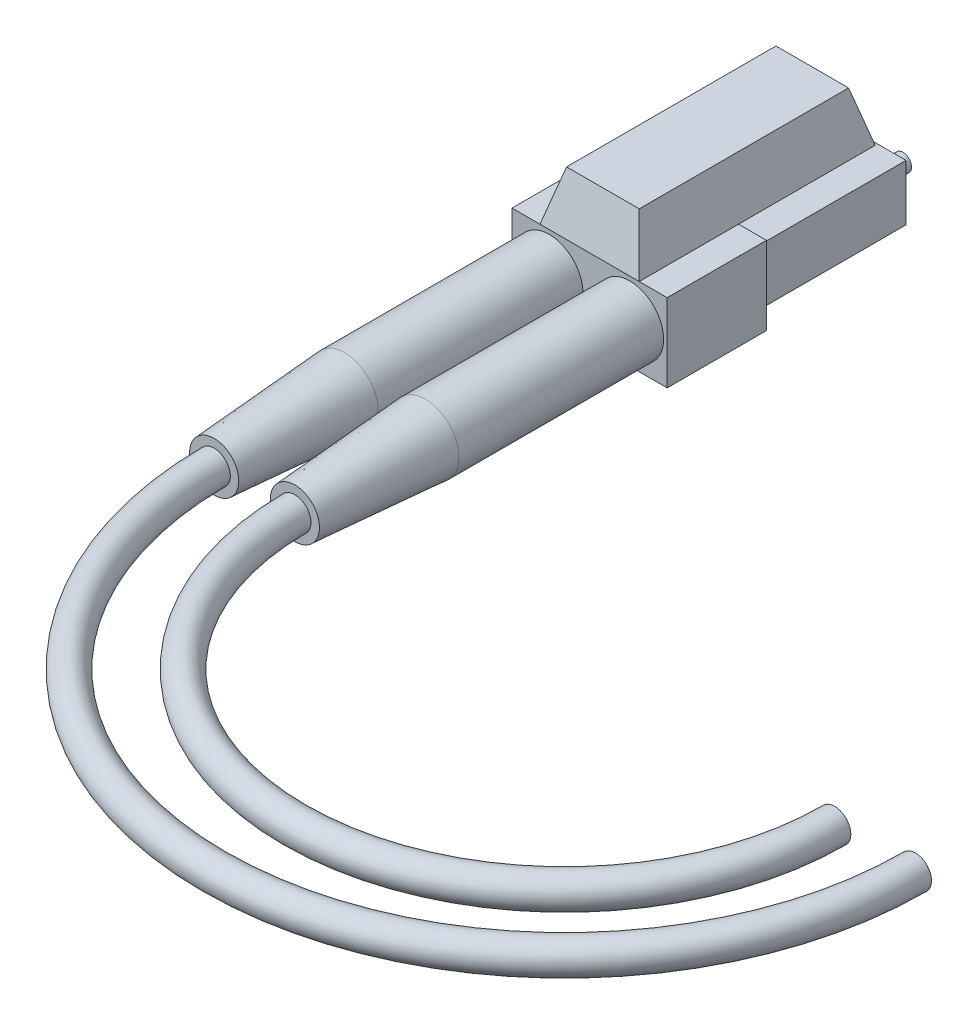
SolidWorks part; units mm, degrees
ref_plane "Front" through (0, 0, 0) normal (0, 0, 1) x (1, 0, 0)
ref_plane "Top" through (0, 0, 0) normal (0, 1, 0) x (1, 0, 0)
ref_plane "Right" through (0, 0, 0) normal (1, 0, 0) x (0, 0, -1)
sketch "Sketch1" plane through (0, 0, 0) normal (0, 0, 1) x (1, 0, 0)
  line L0 (0.9959, 4.5) -> (5.4959, 4.5)
  line L1 (-5.5041, 4.5) -> (-1.0041, 4.5)
  line L2 (-5.5041, 4.5) -> (-5.5041, 0)
  line L3 (-5.5041, 0) -> (-1.0041, 0)
  line L4 (-1.0041, 4.5) -> (-1.0041, 0)
  line L5 (0.9959, 4.5) -> (0.9959, 0)
  line L6 (0.9959, 0) -> (5.4959, 0)
  line L7 (5.4959, 4.5) -> (5.4959, 0)
  dimension "D1" = 2
extrude "Boss-Extrude1" add sketch "Sketch1" against normal blind 12
sketch "Sketch2" plane through (0, 0, -12) normal (0, 0, -1) x (-1, 0, 0)
  circle A0 centre (3.25, 2.25) radius 0.6917
  circle A1 centre (-3.25, 2.25) radius 0.6917
  dimension "D1" = 2
extrude "Boss-Extrude2" add sketch "Sketch2" along normal blind 2
sketch "Sketch3" plane through (0, 0, 0) normal (0, 0, 1) x (1, 0, 0)
  line L1 (-6.25, -1) -> (6.25, -1)
  line L2 (-6.25, -1) -> (-6.25, 5.3)
  line L3 (-6.25, 5.3) -> (6.25, 5.3)
  line L4 (6.25, -1) -> (6.25, 5.3)
extrude "Boss-Extrude3" add sketch "Sketch3" along normal blind 8 contours L1 L4 L3 L2
sketch "Sketch4" plane through (0, 0, 8) normal (0, 0, 1) x (1, 0, 0)
  circle A0 centre (3.25, 2.25) radius 2.715
  circle A1 centre (-3.25, 2.25) radius 2.715
extrude "Boss-Extrude4" add sketch "Sketch4" along normal blind 16.5
sketch "Sketch5" plane through (0, 0, 24.5) normal (0, 0, 1) x (1, 0, 0)
  circle A0 centre (-3.25, 2.25) radius 2.715
  circle A1 centre (3.25, 2.25) radius 2.715
extrude "Boss-Extrude5" add sketch "Sketch5" along normal blind 10.5 draft 4
sketch "Sketch6" plane through (0, 0, 35) normal (0, 0, 1) x (1, 0, 0)
  circle A0 centre (3.25, 2.25) radius 1.375
  circle A1 centre (-3.25, 2.25) radius 1.375
extrude "Boss-Extrude6" [suppressed] add sketch "Sketch6" along normal blind 23
sketch "Sketch7" [suppressed] plane through (0, 0, 58) normal (0, 0, 1) x (1, 0, 0)
  circle A0 centre (3.25, 2.25) radius 1
  circle A1 centre (-3.25, 2.25) radius 1
extrude "Boss-Extrude7" [suppressed] add sketch "Sketch7" along normal blind 25
sketch "Sketch8" plane through (0, 5.3, 0) normal (0, 1, 0) x (1, 0, 0)
  line L0 (-6.25, -8) -> (6.25, -8) construction
  line L1 (4, -8) -> (-4, -8)
  line L2 (4, -8) -> (4, 11.0144)
  line L3 (4, 11.0144) -> (-4, 11.0144)
  line L4 (-4, -8) -> (-4, 11.0144)
extrude "Boss-Extrude8" add sketch "Sketch8" along normal blind 4 draft 15
sketch "Sketch9" plane through (0, 0, 35) normal (0, 0, 1) x (1, 0, 0)
  circle A0 centre (-3.25, 2.25) radius 1.3
  circle A1 centre (3.25, 2.25) radius 1.3
ref_plane "Plane1" through (0, 2.25, 0) normal (0, -1, 0) x (1, 0, 0)
sketch "Sketch10" plane through (0, 2.25, 0) normal (0, -1, 0) x (1, 0, 0)
  line L0 (-1.2692, 35) -> (1.2692, 35) construction
  line L1 (0, 35) -> (50, 35) construction
  arc A0 (0, 35) -> (50, 35) centre (25, 35) cw
sweep "Sweep1" add profiles "Sketch9" path "Sketch10"
